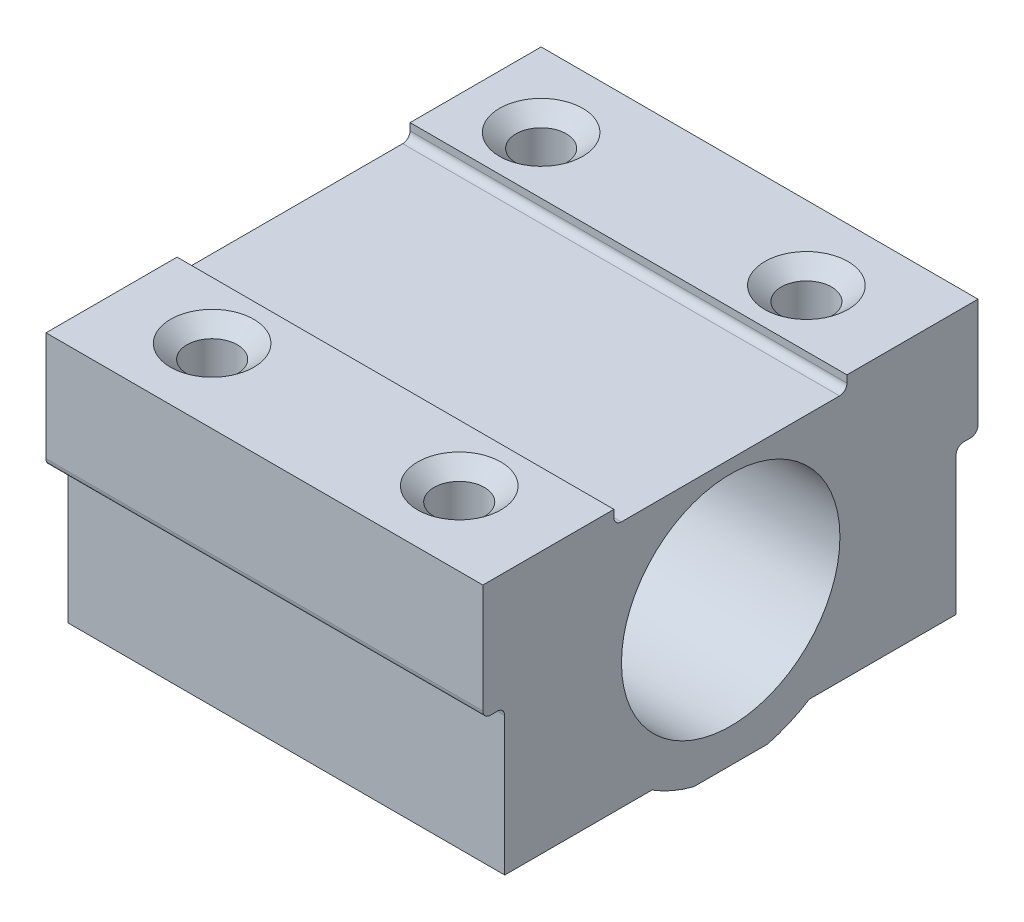
SolidWorks part; units mm, degrees
ref_plane "Front Plane" through (0, 0, 0) normal (0, 0, 1) x (1, 0, 0)
ref_plane "Top Plane" through (0, 0, 0) normal (0, 1, 0) x (1, 0, 0)
ref_plane "Right Plane" through (0, 0, 0) normal (1, 0, 0) x (0, 0, -1)
sketch "Sketch1" plane through (0, 0, 0) normal (1, 0, 0) x (0, 0, -1)
  line L0 (32.5, 0) -> (34, 0)
  line L1 (0, 0) -> (1.5, 0)
  line L2 (0, 0) -> (0, 7.4937)
  line L3 (9, 7) -> (25, 7)
  line L4 (34, 0) -> (34, 7.4937)
  line L6 (1.5, 0) -> (1.5, -10)
  line L7 (1.5, -10) -> (11.6114, -10)
  line L8 (32.5, 0) -> (32.5, -10)
  line L10 (0, 7.4937) -> (0, 8)
  line L11 (0, 8) -> (9, 8)
  line L12 (9, 7) -> (9, 8)
  line L14 (34, 7.4937) -> (34, 8)
  line L15 (34, 8) -> (25, 8)
  line L16 (25, 7) -> (25, 8)
  line L17 (14.4865, -11.2376) -> (19.5495, -11.2376)
  line L18 (22.4246, -10) -> (32.5, -10)
  circle A0 centre (17.018, -1.398) radius 7.5
  arc A1 (11.6114, -10) -> (14.4865, -11.2376) centre (17.018, -1.398) ccw
  arc A2 (19.5495, -11.2376) -> (22.4246, -10) centre (17.018, -1.398) ccw
  point P19 (29.5, 8)
  dimension "D7" = 15
  dimension "D8" = 20.32
  dimension "D1" = 34
  dimension "D2" = 18
  dimension "D3" = 1.5
  dimension "D4" = 10
  dimension "D5" = 1
  dimension "D6" = 9
  dimension "D9" = 9.398
  dimension "D10" = 17.018
extrude "Boss-Extrude1" add sketch "Sketch1" along normal blind 30
hole_wizard "CSK for #4 Flat Head Machine Screw (100)1" positions "Sketch3" profile "Sketch4" countersink size "#4" standard "ANSI Inch"
sketch "Sketch3" plane through (0, 8, 0) normal (0, 1, 0) x (1, 0, 0)
  line L0 (0, 34) -> (0, 25) construction
  line L1 (30, 34) -> (0, 34) construction
  line L2 (30, 0) -> (0, 0) construction
  point P0 (5.08, 28.92)
  point P2 (23.2957, 28.92)
  point P4 (23.2957, 5.08)
  point P6 (6.3293, 5.08)
  dimension "D1" = 5.08
  dimension "D2" = 5.08
  dimension "D3" = 5.08
sketch "Sketch4" plane through (5.08, 8, -28.92) normal (1, 0, 0) x (0, 0, 1)
  line L0 (0, 0) -> (0, 7.3878)
  line L1 (0, 7.3878) -> (1.7272, 6.35)
  line L2 (1.7272, 6.35) -> (1.7272, 0.9484)
  line L3 (1.7272, 0.9484) -> (2.8575, 0)
  line L5 (2.8575, 0) -> (0, 0)
  line L6 (-1.7272, 0.9484) -> (-2.8575, 0) construction
  line L10 (0, 7.3878) -> (-1.7272, 6.35) construction
  line L11 (0, -6.35) -> (0, 107.95) construction
  dimension "Hole Dia." = 3.4544
  dimension "Hole Depth" = 6.35
  dimension "Near C'Sink Dia." = 5.715
  dimension "Near C'Sink Angle" = 100
  dimension "Drill Angle" = 118
fillet "Fillet1" radius 0.508 6 edges at (15, 7, -25) (15, 7, -9) (15, 0, -34) (15, 0, -32.5) (15, 0, 0) (15, 0, -1.5)
